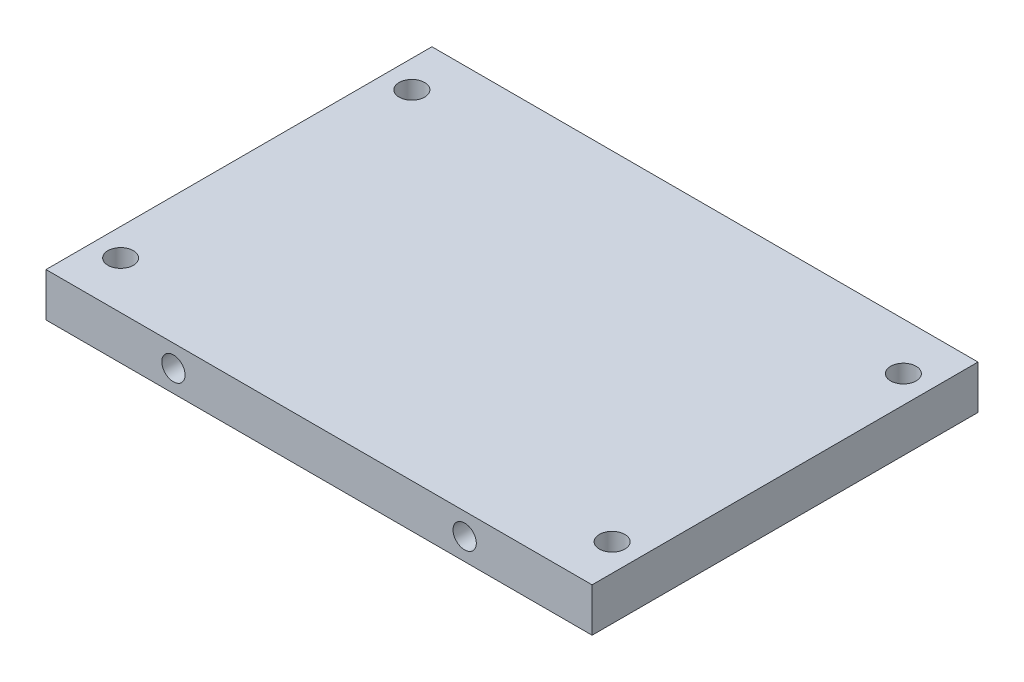
SolidWorks part; units mm, degrees
other "Markup1"
sketch "Sketch5" plane through (75, 6, 0) normal (0.0216, 0.9138, -0.4056) x (-0.9986, 0, -0.0531)
sketch "Sketch6" plane through (75, 6, 0) normal (0.0216, 0.9138, -0.4056) x (-0.9986, 0, -0.0531)
ref_plane "Front Plane" through (0, 0, 0) normal (0, 0, 1) x (1, 0, 0)
ref_plane "Top Plane" through (0, 0, 0) normal (0, 1, 0) x (1, 0, 0)
ref_plane "Right Plane" through (0, 0, 0) normal (1, 0, 0) x (0, 0, -1)
sketch "Sketch1" plane through (0, 0, 0) normal (0, 1, 0) x (1, 0, 0)
  line L0 (0, 0) -> (75, 0)
  line L2 (0, 0) -> (0, -53)
  line L4 (75, 0) -> (75, -53)
  line L5 (0, -53) -> (75, -53)
  line L7 (0, 0) -> (0, -53)
  line L9 (75, 0) -> (75, -53)
  line L12 (71.25, -4.75) -> (71.25, -6.5) construction
  line L13 (37.5, -26.5) -> (75, -26.5) construction
  circle A4 centre (71.25, -6.5) radius 1.75
  circle A5 centre (3.75, -6.5) radius 1.75
  circle A6 centre (71.25, -46.5) radius 1.75
  circle A7 centre (3.75, -46.5) radius 1.75
  point P12 (27.5, 15)
  point P18 (32.25, 15)
  dimension "D6" = 3.5
  dimension "D2" = 53
extrude "Boss-Extrude8" add sketch "Sketch1" along normal blind 6 contours A7 A6 L4 A4 A5 L2 region at (37.5, 0, 26.5)
sketch "Sketch8" plane through (0, 0, 53) normal (0, 0, 1) x (1, 0, 0)
  line L0 (37.5, 6) -> (37.5, 0) construction
  line L1 (0, 6) -> (75, 6) construction
  line L2 (0, 0) -> (75, 0) construction
  line L3 (17.5, 3) -> (57.5, 3)
  circle A0 centre (17.5, 3) radius 1.6
  circle A1 centre (57.5, 3) radius 1.6
  point P9 (37.5, 3)
  dimension "D2" = 3.2
  dimension "D3" = 3.2
  dimension "D1" = 40
extrude "Cut-Extrude1" cut sketch "Sketch8" against normal blind 10 contours A0 | A1 region at (57.5, 4.5547, 53) region at (15.9453, 3, 53)
extrude "Cut-Extrude2" cut sketch "Sketch8<3>" along normal blind 10 from surface contours A0 | A1 region at (57.5, 4.5547, 53) region at (15.9453, 3, 53) starting at face at (37.5, 3, 0)
sketch "Sketch8<3>" plane through (0, 0, 53) normal (0, 0, 1) x (1, 0, 0) same geometry as "Sketch8"
